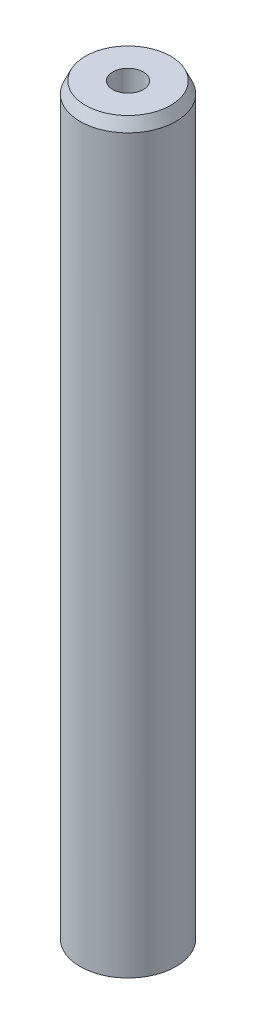
SolidWorks part; units mm, degrees
ref_plane "Front Plane" through (0, 0, 0) normal (0, 0, 1) x (1, 0, 0)
ref_plane "Top Plane" through (0, 0, 0) normal (0, 1, 0) x (1, 0, 0)
ref_plane "Right Plane" through (0, 0, 0) normal (1, 0, 0) x (0, 0, -1)
sketch "Sketch1" plane through (0, 0, 0) normal (0, 1, 0) x (1, 0, 0)
  circle A0 centre (0, 0) radius 12.5
  dimension "SHAFT_OD" = 25
extrude "Boss-Extrude1" add sketch "Sketch1" along normal blind 195.2822
sketch "Sketch2" plane through (0, 0, 0) normal (0, 1, 0) x (1, 0, 0)
  circle A0 centre (0, 0) radius 3.9848
  dimension "BORE_D" = 7.9696
extrude "Cut-Extrude1" cut sketch "Sketch2" along normal through all
chamfer "Chamfer1" distance 2.9484 angle 25.186 2 edges at (0, 195.2822, 12.5) (0, 0, 12.5) first distance on face at (0, 195.2822, 12.5) first distance on face at (0, 0, 3.9848)
